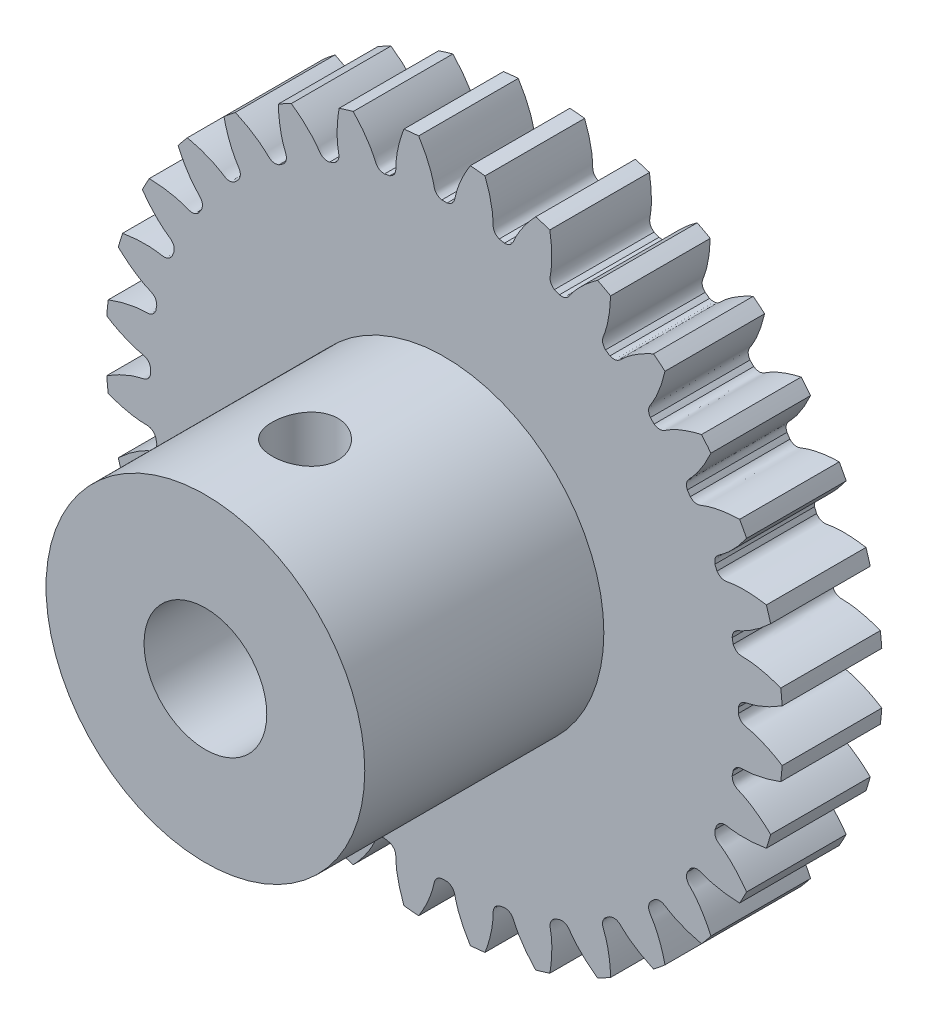
SolidWorks part; units mm, degrees
ref_plane "前视基准面" through (0, 0, 0) normal (0, 0, 1) x (1, 0, 0)
ref_plane "上视基准面" through (0, 0, 0) normal (0, 1, 0) x (1, 0, 0)
ref_plane "右视基准面" through (0, 0, 0) normal (1, 0, 0) x (0, 0, -1)
other "Configuration Table"
sketch "草图1" plane through (0, 0, 0) normal (0, 0, 1) x (1, 0, 0)
  circle A0 centre (0, 0) radius 8.5
extrude "凸台-拉伸1" add sketch "草图1" along normal blind 2.5
ref_axis "基准轴1" through (0, 0, 2.5) along (0, 0, -1)
sketch "草图2" plane through (0, 0, 0) normal (0, 0, 1) x (1, 0, 0)
  line L0 (0, 0) -> (0, 8.5) construction
  circle A0 centre (0, 0) radius 8.5 construction
  arc A1 (0.067, 7.3747) -> (-0.067, 7.3747) centre (0, 0) ccw
  arc A2 (1.6765, 9.6348) -> (-1.6765, 9.6348) centre (0, 0) ccw
  spline S0 degree 3 poles (0.067, 7.3747) (0.2444, 7.4176) (0.2542, 7.5462) (0.2867, 7.6804) (0.2952, 7.7127) (0.3051, 7.7477) (0.3166, 7.7854) (0.3299, 7.8257) (0.3449, 7.8686) (0.3618, 7.9139) (0.3807, 7.9618) (0.4017, 8.012) (0.4249, 8.0645) (0.4505, 8.1193) (0.4785, 8.1763) (0.509, 8.2353) (0.5421, 8.2964) (0.5779, 8.3594) (0.6164, 8.4243) (0.6579, 8.491) (0.7023, 8.5593) (0.7498, 8.6292) (0.8004, 8.7006) (0.8542, 8.7734) (0.9113, 8.8475) (0.9717, 8.9228) (1.0356, 8.9992) (1.1029, 9.0765) (1.1738, 9.1547) (1.2483, 9.2337) (1.3265, 9.3133) (1.4084, 9.3934) (1.5241, 9.5022) (1.6145, 9.5821) (1.6765, 9.6348) knots 0 0 0 0 0.124533 0.135329 0.147193 0.160126 0.174128 0.189198 0.205337 0.222544 0.24082 0.260164 0.280577 0.302059 0.324609 0.348227 0.372914 0.39867 0.425494 0.453386 0.482348 0.512377 0.543476 0.575642 0.608878 0.643181 0.678554 0.714995 0.752504 0.791082 0.830729 0.871444 0.913227 1 1 1 1
  spline S1 degree 3 poles (-0.067, 7.3747) (-0.2444, 7.4176) (-0.2542, 7.5462) (-0.2867, 7.6804) (-0.2952, 7.7127) (-0.3051, 7.7477) (-0.3166, 7.7854) (-0.3299, 7.8257) (-0.3449, 7.8686) (-0.3618, 7.9139) (-0.3807, 7.9618) (-0.4017, 8.012) (-0.4249, 8.0645) (-0.4505, 8.1193) (-0.4785, 8.1763) (-0.509, 8.2353) (-0.5421, 8.2964) (-0.5779, 8.3594) (-0.6164, 8.4243) (-0.6579, 8.491) (-0.7023, 8.5593) (-0.7498, 8.6292) (-0.8004, 8.7006) (-0.8542, 8.7734) (-0.9113, 8.8475) (-0.9717, 8.9228) (-1.0356, 8.9992) (-1.1029, 9.0765) (-1.1738, 9.1547) (-1.2483, 9.2337) (-1.3265, 9.3133) (-1.4084, 9.3934) (-1.5241, 9.5022) (-1.6145, 9.5821) (-1.6765, 9.6348) knots 0 0 0 0 0.124533 0.135329 0.147193 0.160126 0.174128 0.189198 0.205337 0.222544 0.24082 0.260164 0.280577 0.302059 0.324609 0.348227 0.372914 0.39867 0.425494 0.453386 0.482348 0.512377 0.543476 0.575642 0.608878 0.643181 0.678554 0.714995 0.752504 0.791082 0.830729 0.871444 0.913227 1 1 1 1
extrude "切除-拉伸1" cut sketch "草图2" along normal through all
pattern_circular "阵列(圆周)1" count 32 every 11.25 about axis through (0, 0, 2.5) along (0, 0, -1) of "切除-拉伸1"
sketch "草图3" plane through (0, 0, 0) normal (0, 0, 1) x (1, 0, 0)
  circle A0 centre (0, 0) radius 8 construction
  dimension "Dn" = 16
sketch "草图5" plane through (0, 0, 2.5) normal (0, 0, 1) x (1, 0, 0)
  circle A0 centre (0, 0) radius 4
  dimension "D1" = 8
extrude "凸台-拉伸2" add sketch "草图5" along normal blind 6
sketch "草图4" plane through (0, 0, 0) normal (0, 0, -1) x (-1, 0, 0)
  circle A0 centre (0, 0) radius 1.54
  dimension "D1" = 3.08
extrude "切除-拉伸2" cut sketch "草图4" against normal up to next
sketch "草图6" plane through (0, 0, 0) normal (0, 1, 0) x (1, 0, 0)
  line L0 (0, -8.5) -> (0, -2.5) construction
  line L1 (-4, -8.5) -> (4, -8.5) construction
  circle A0 centre (0, -6) radius 0.825
  dimension "D1" = 1.65
  dimension "D2" = 2.5
extrude "切除-拉伸3" cut sketch "草图6" along normal up to next
